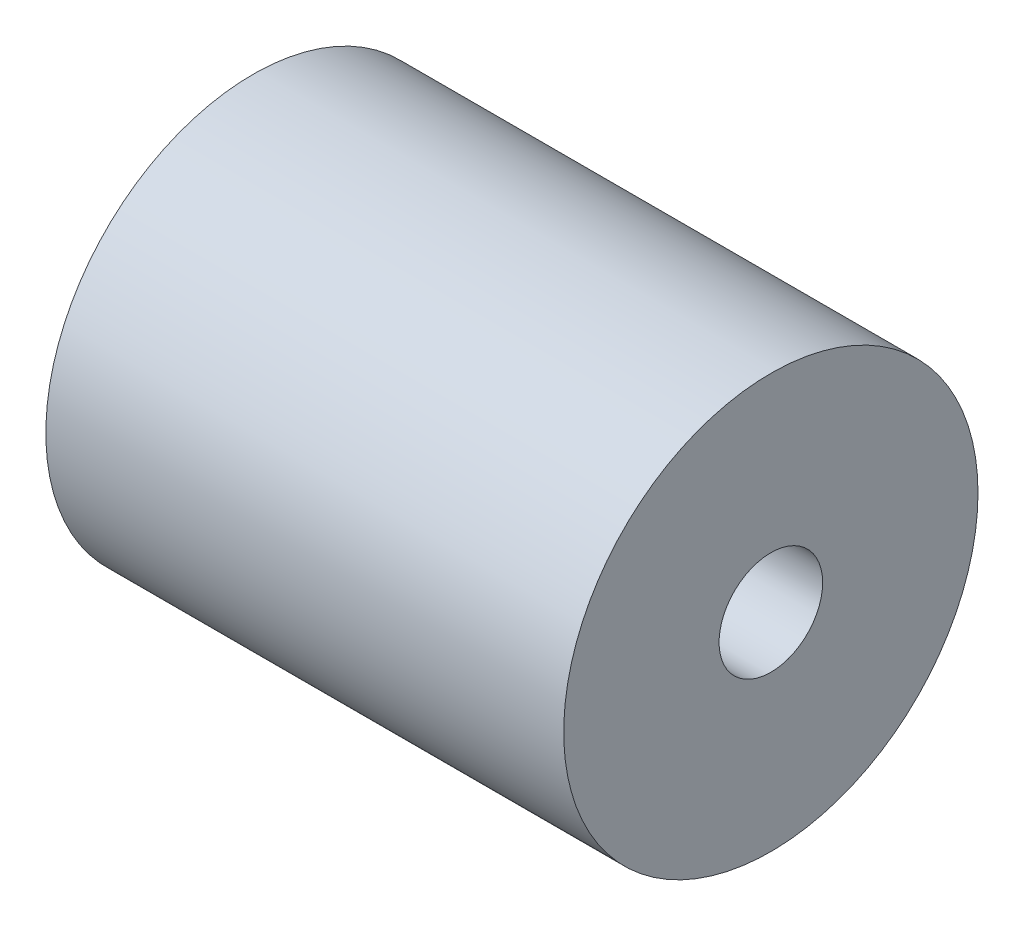
SolidWorks part; units mm, degrees
material "1060 Alloy"
ref_plane "Front Plane" through (0, 0, 0) normal (0, 0, 1) x (1, 0, 0)
ref_plane "Top Plane" through (0, 0, 0) normal (0, 1, 0) x (1, 0, 0)
ref_plane "Right Plane" through (0, 0, 0) normal (1, 0, 0) x (0, 0, -1)
sketch "Sketch1" plane through (0, 0, 0) normal (1, 0, 0) x (0, 0, -1)
  circle A0 centre (0, 0) radius 10
  circle A1 centre (0, 0) radius 2.5
  dimension "D1" = 20
  dimension "D2" = 5
extrude "Boss-Extrude1" add sketch "Sketch1" along normal blind 17.5 and the other way blind 7.5
sketch "Sketch2" plane through (0, 0, 0) normal (0, 1, 0) x (1, 0, 0)
  line L0 (5, 10) -> (5, -4.0374) construction
  line L1 (17.5, 10) -> (-7.5, 10) construction
  circle A0 centre (13.5, 0) radius 1.5
  circle A1 centre (-3.5, 0) radius 1.5
  dimension "D1" = 3
  dimension "D2" = 17
extrude "Cut-Extrude1" [suppressed] cut sketch "Sketch2" along normal up to next from offset 8
sketch "Sketch4" [suppressed] plane through (0, 8, 0) normal (0, 1, 0) x (1, 0, 0)
  line L0 (17.5, -10) -> (17.5, 10) construction
  line L1 (14.5, 0.5774) -> (13.5, 1.1547)
  line L2 (13.5, 1.1547) -> (12.5, 0.5774)
  line L3 (12.5, 0.5774) -> (12.5, -0.5774)
  line L4 (12.5, -0.5774) -> (13.5, -1.1547)
  line L5 (13.5, -1.1547) -> (14.5, -0.5774)
  line L6 (14.5, -0.5774) -> (14.5, 0.5774)
  line L7 (5, 10) -> (5, -10) construction
  line L8 (17.5, 10) -> (-7.5, 10) construction
  line L9 (-7.5, -10) -> (17.5, -10) construction
  line L10 (-4.5, -0.5774) -> (-4.5, 0.5774)
  line L11 (-3.5, -1.1547) -> (-4.5, -0.5774)
  line L12 (-2.5, -0.5774) -> (-3.5, -1.1547)
  line L13 (-2.5, 0.5774) -> (-2.5, -0.5774)
  line L14 (-3.5, 1.1547) -> (-2.5, 0.5774)
  line L15 (-4.5, 0.5774) -> (-3.5, 1.1547)
  circle A0 centre (13.5, 0) radius 1 construction
  circle A1 centre (-3.5, 0) radius 1 construction
  dimension "D1" = 2
extrude "Cut-Extrude2" [suppressed] cut sketch "Sketch4" against normal blind 1
pattern_circular "CirPattern1" [suppressed] count 2 every 75 of bodies 103
sketch "Sketch5" plane through (0, 0, 0) normal (1, 0, 0) x (0, 0, -1)
  circle A0 centre (0, 0) radius 10 construction
  circle A1 centre (0, 0) radius 10
curve "Helix/Spiral1" pitch 2 height 10 turns 5
sketch "Sketch7" plane through (0, 0, 0) normal (0, 1, 0) x (1, 0, 0)
  line L0 (-0.25, 2.5) -> (-7.5, 2.5) construction
  line L1 (-0.25, 10) -> (0.25, 10)
  line L2 (-0.25, 10) -> (-0.25, 2.5)
  line L3 (-0.25, 2.5) -> (0.25, 2.5)
  line L4 (0.25, 10) -> (0.25, 2.5)
  point P4 (0, 10)
  dimension "D1" = 0.5
sweep "Cut-Sweep2" [suppressed] cut profiles "Sketch7" path "Helix/Spiral1"
fillet "Fillet1" [suppressed] radius 0.4
